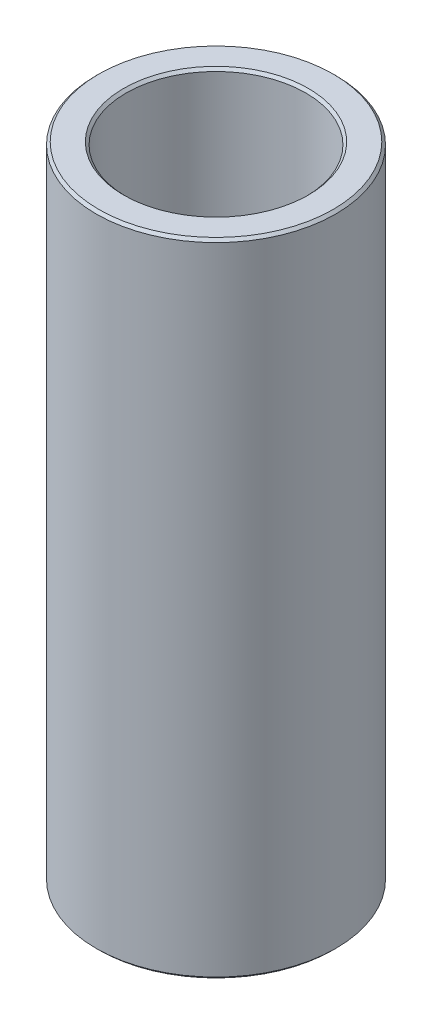
SolidWorks part; units mm, degrees
ref_plane "Front Plane" through (0, 0, 0) normal (0, 0, 1) x (1, 0, 0)
ref_plane "Top Plane" through (0, 0, 0) normal (0, 1, 0) x (1, 0, 0)
ref_plane "Right Plane" through (0, 0, 0) normal (1, 0, 0) x (0, 0, -1)
sketch "Sketch1" plane through (0, 0, 0) normal (0, 1, 0) x (1, 0, 0)
  circle A0 centre (0, 0) radius 40
  dimension "SLEEVE_OD" = 80
extrude "Boss-Extrude1" add sketch "Sketch1" along normal blind 214.0091
sketch "Sketch2" plane through (0, 0, 0) normal (0, 1, 0) x (1, 0, 0)
  circle A0 centre (0, 0) radius 29.9631
  dimension "BORE_D" = 59.9262
extrude "Cut-Extrude1" cut sketch "Sketch2" along normal through all
chamfer "Chamfer1" distance 0.8745 angle 45 4 edges at (0, 214.0091, 29.9631) (0, 0, 29.9631) (0, 0, 40) (0, 214.0091, 40)
